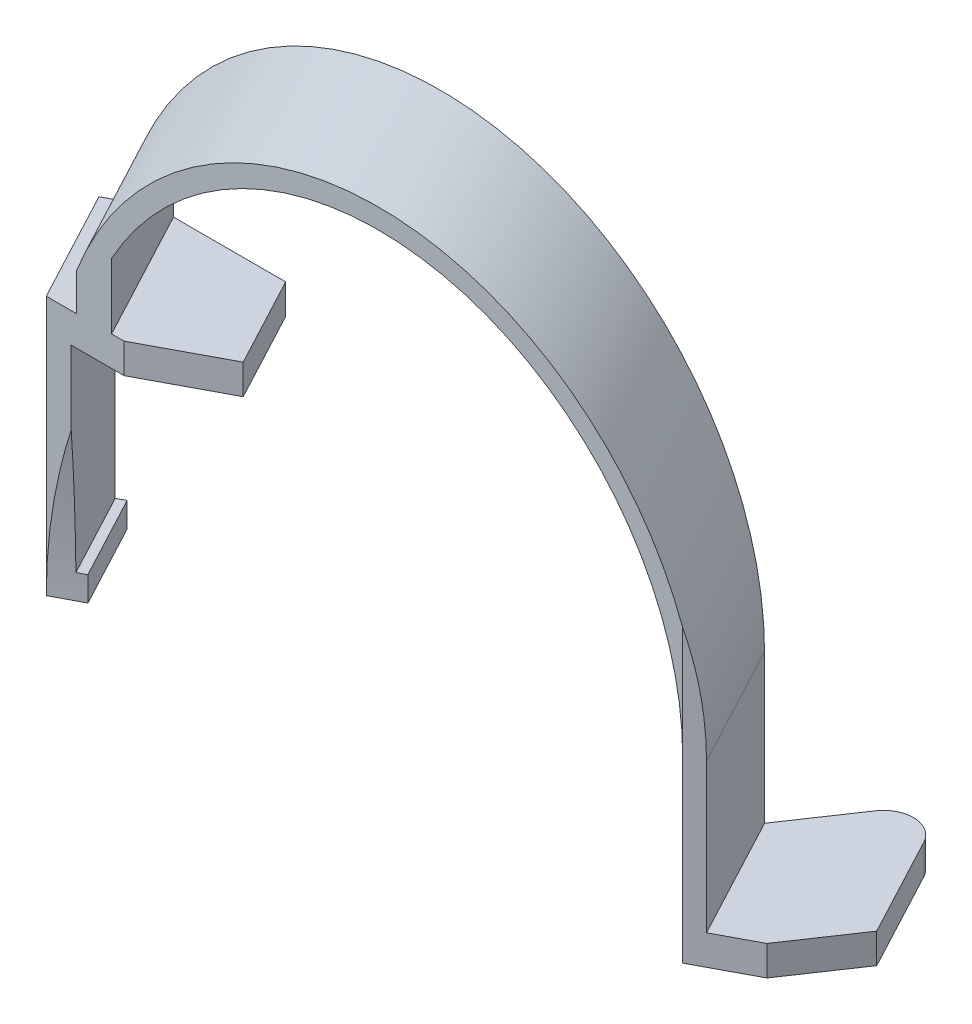
SolidWorks part; units mm, degrees
ref_plane "Plano frontal" through (0, 0, 0) normal (0, 0, 1) x (1, 0, 0)
ref_plane "Plano superior" through (0, 0, 0) normal (0, 1, 0) x (1, 0, 0)
ref_plane "Plano direito" through (0, 0, 0) normal (1, 0, 0) x (0, 0, -1)
sketch "Esboço1" plane through (0, 0, 0) normal (0, 0, 1) x (1, 0, 0)
  line L3 (30.5, 0) -> (30.5, -17.9)
  line L5 (32.5, -14.9) -> (32.5, 0)
  line L6 (32.5, -14.9) -> (45.5, -14.9)
  line L7 (45.5, -14.9) -> (45.5, -17.9)
  line L8 (45.5, -17.9) -> (30.5, -17.9)
  line L11 (0, 32.5) -> (0, -17.9) construction
  line L18 (-33.3, -17.9) -> (-30.8, -17.9)
  line L19 (-30.8, -15.4161) -> (-30.8, 5.1)
  line L20 (-30.8, 5.1) -> (-26.75, 5.1)
  line L21 (-26.75, 5.1) -> (-26.75, 14.6522) construction
  line L22 (-33.3, -17.9) -> (-33.3, 8.1)
  line L23 (-33.3, 8.1) -> (-30.25, 8.1)
  line L24 (-30.25, 8.1) -> (-30.25, 11.8822)
  line L25 (-26.75, 5.1) -> (-15.5, 5.1)
  line L26 (-15.5, 5.1) -> (-15.5, 8.1)
  line L27 (-15.5, 8.1) -> (-26.75, 8.1)
  line L28 (-26.75, 8.1) -> (-26.75, 14.6522)
  line L29 (-30.8, -17.9) -> (-29.8, -17.9)
  line L30 (-29.8, -17.9) -> (-29.8, -15.4161)
  line L31 (-29.8, -15.4161) -> (-30.8, -15.4161)
  circle A0 centre (0, 0) radius 30.5 construction
  arc A1 (-30.25, 11.8822) -> (32.5, 0) centre (0, 0) cw
  arc A2 (-26.75, 14.6522) -> (30.5, 0) centre (0, 0) cw
  dimension "D1" = 61
  dimension "D2" = 3.5
  dimension "D3" = 2
  dimension "D4" = 17.9
  dimension "D5" = 3
  dimension "D6" = 15
  dimension "D7" = 57.25
  dimension "D8" = 50.4
  dimension "D9" = 2.5
  dimension "D10" = 3
  dimension "D11" = 63.8
  dimension "D12" = 23
  dimension "D13" = 11.25
  dimension "D14" = 46
  dimension "D15" = 3.5
  dimension "D16" = 60.75
extrude "Ressalto-extrusão1" [suppressed] add sketch "Esboço1" against normal blind 15
sketch "Esboço2" plane through (0, 0, 0) normal (0, 1, 0) x (1, 0, 0)
  line L0 (0, 0) -> (-7.0421, 13.2442)
  line L1 (0, -55) -> (0, 55) construction
  dimension "D1" = 28
  dimension "D2" = 15
sweep "Varredura2" add profiles "Esboço1<3>" path "Esboço2"
sketch "Esboço1<3>" plane through (0, 0, 0) normal (0, 0, 1) x (1, 0, 0) same geometry as "Esboço1"
sketch "Esboço4" plane through (0, -17.9, 0) normal (0, -1, 0) x (1, 0, 0)
  line L0 (42.1939, -6.2178) -> (30.5, 0)
  line L1 (45.5, 0) -> (38.4579, -13.2442) construction
  line L2 (30.5, 0) -> (45.5, 0)
  line L3 (45.5, 0) -> (42.1939, -6.2178)
  dimension "D1" = 28
extrude "Corte-extrusão1" cut sketch "Esboço4" against normal through all
sketch "Esboço5" plane through (-25.9606, 0, 13.8035) normal (-0.8829, 0, 0.4695) x (0.4695, 0, 0.8829)
  line L0 (-30.6334, -17.9) -> (-25.1334, -17.9)
  line L1 (-15.6334, -17.9) -> (-30.6334, -17.9) construction
  line L2 (-26.6334, -17.9) -> (-30.6334, 7.1) construction
  line L3 (-30.6334, 8.1) -> (-30.6334, -17.9) construction
  line L4 (-30.6334, 7.1) -> (-30.6334, -17.9)
  line L5 (-15.6334, 8.1) -> (-15.6334, -17.9) construction
  line L6 (-13.1695, 4.6798) -> (-13.1695, -17.9)
  line L7 (-13.1695, -17.9) -> (-15.6334, -17.9)
  line L8 (-15.6334, 8.1) -> (-30.6334, 8.1) construction
  line L9 (-25.1334, -17.9) -> (-25.1334, -2.9)
  arc A1 (-15.6334, -17.9) -> (-13.1695, 4.6798) centre (89.0609, -17.9) cw
  arc A2 (-25.1334, -2.9) -> (-30.6334, 7.1) centre (-36.9743, -2.9) ccw
  dimension "D1" = 4
  dimension "D2" = 1
  dimension "D3" = 5.5
  dimension "D4" = 9.5
  dimension "D6" = 15
extrude "Corte-extrusão2" cut sketch "Esboço5" against normal through all
chamfer "Chanfro1" distance 10 angle 28 1 edges at (-15.5, 6.6, 0) first distance on face at (-17.9739, 8.3446, 0)
sketch "Esboço6" plane through (-24.0116, 0, 12.7672) normal (0.8829, 0, -0.4695) x (-0.4695, 0, -0.8829)
  line L0 (29.2015, 11.8822) -> (29.2015, 8.1) construction
  line L1 (33.7699, 17.7241) -> (28.4015, 17.7241)
  line L2 (33.7699, 17.7241) -> (33.7699, -0.6101)
  line L3 (33.7699, -0.6101) -> (28.4015, -0.6101)
  line L4 (28.4015, 17.7241) -> (28.4015, -0.6101)
  line L5 (27.5584, 8.1) -> (27.5584, 14.6522) construction
  dimension "D1" = 0.8
  dimension "D2" = 0.8432
extrude "Corte-extrusão3" cut sketch "Esboço6" against normal blind 5 and the other way blind 5
sketch "Esboço7" plane through (0, -14.9, 0) normal (0, 1, 0) x (1, 0, 0)
  line L0 (25.4579, 13.2442) -> (32.7274, 24.0217)
  line L1 (32.7274, 24.0217) -> (38.4579, 13.2442)
  line L2 (38.4579, 13.2442) -> (25.4579, 13.2442)
  line L3 (42.1939, 6.2178) -> (38.4579, 13.2442) construction
  line L4 (32.0592, 0.829) -> (42.1939, 6.2178) construction
  dimension "D1" = 28
extrude "Ressalto-extrusão2" add sketch "Esboço7" against normal up to surface (3 mm away) up to face at (33.6524, -17.9, -8.1766)
chamfer "Chanfro2" distance 7 angle 28 1 edges at (42.1939, -16.4, -6.2178) first distance on face at (34.1752, -6.9661, -1.9542)
fillet "Filete2" radius 3 1 edges at (32.7274, -16.4, -24.0217)
